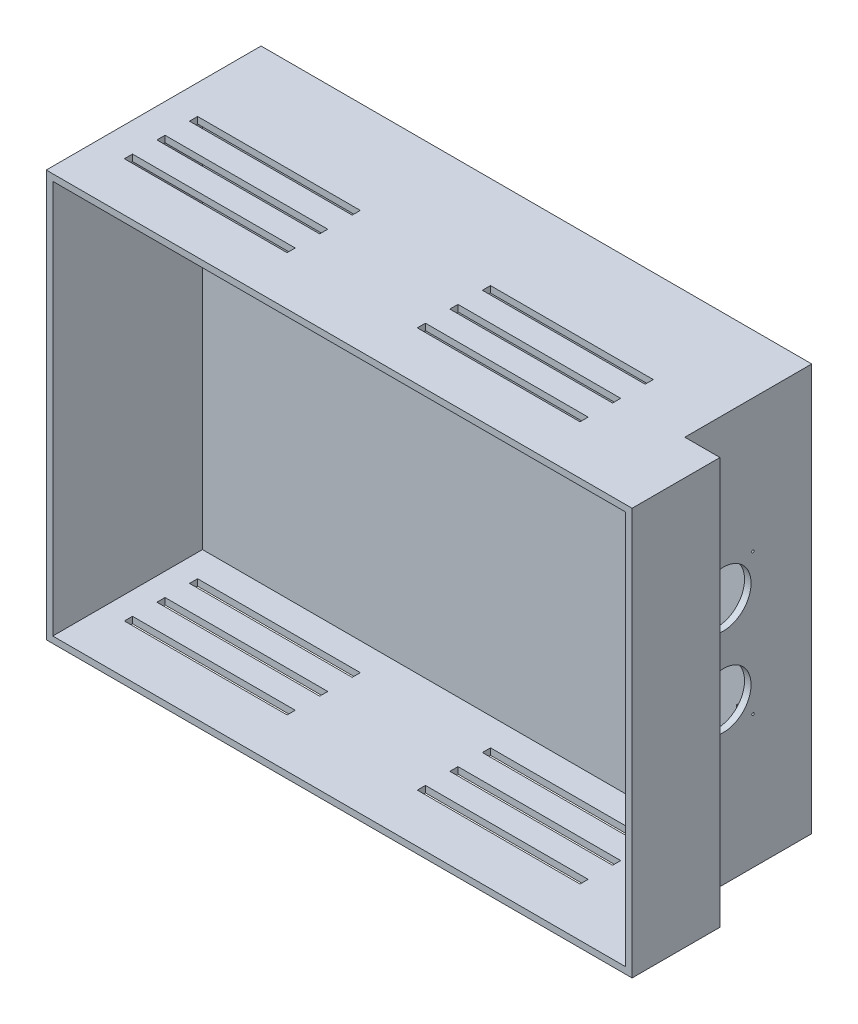
SolidWorks part; units mm, degrees
ref_plane "前视基准面" through (0, 0, 0) normal (0, 0, 1) x (1, 0, 0)
ref_plane "上视基准面" through (0, 0, 0) normal (0, 1, 0) x (1, 0, 0)
ref_plane "右视基准面" through (0, 0, 0) normal (1, 0, 0) x (0, 0, -1)
sketch "草图2" plane through (0, 0, 0) normal (0, 0, 1) x (1, 0, 0)
  line L1 (-90, 62.5) -> (90, 62.5)
  line L2 (-90, 62.5) -> (-90, -62.5)
  line L3 (-90, -62.5) -> (90, -62.5)
  line L4 (90, 62.5) -> (90, -62.5)
  line L5 (-90, 62.5) -> (90, -62.5) construction
  line L6 (-90, -62.5) -> (90, 62.5) construction
  point P0 (0, 0)
  dimension "D1" = 180
  dimension "D2" = 125
extrude "凸台-拉伸1" add sketch "草图2" along normal blind 66
sketch "草图3" plane through (0, 0, 0) normal (0, 0, -1) x (-1, 0, 0)
  line L1 (87, -59.5) -> (-50, -59.5)
  line L2 (87, -59.5) -> (87, 59.5)
  line L3 (87, 59.5) -> (-50, 59.5)
  line L4 (-50, -59.5) -> (-50, 59.5)
  line L5 (-90, 62.5) -> (90, 62.5) construction
  line L6 (90, 62.5) -> (90, -62.5) construction
  line L7 (90, -62.5) -> (-90, -62.5) construction
  line L9 (-90, -62.5) -> (-90, 62.5) construction
  dimension "D1" = 3
  dimension "D2" = 3
  dimension "D3" = 3
  dimension "D4" = 40
extrude "切除-拉伸1" cut sketch "草图3" against normal blind 18
sketch "草图4" plane through (90, 0, 0) normal (1, 0, 0) x (0, 0, -1)
  line L0 (-39, -62.5) -> (-39, 62.5)
  line L1 (-66, 62.5) -> (-66, -62.5) construction
  line L2 (-66, 62.5) -> (0, 62.5) construction
  line L4 (0, -62.5) -> (0, 62.5)
  line L6 (-66, 62.5) -> (-66, -62.5)
  line L9 (0, 62.5) -> (-39, 62.5)
  line L11 (-39, -62.5) -> (0, -62.5)
  line L14 (0, -62.5) -> (0, 62.5)
  line L15 (0, 62.5) -> (-66, 62.5)
  line L16 (-66, -62.5) -> (0, -62.5)
  dimension "D2" = 27
  dimension "D1" = 0
extrude "切除-拉伸2" cut sketch "草图4" against normal offset from surface (10.8 mm away) 2
shell "抽壳1" thickness 2 removed face at (0, 0, 66)
sketch "草图6" plane through (79.2, 0, 0) normal (1, 0, 0) x (0, 0, -1)
  line L1 (-16.0647, -23.6651) -> (-20.0647, -23.6651)
  line L2 (-16.0647, -23.6651) -> (-16.0647, -19.6651)
  line L3 (-16.0647, -19.6651) -> (-20.0647, -19.6651)
  line L4 (-20.0647, -23.6651) -> (-20.0647, -19.6651)
  line L5 (-34.2212, -23.6651) -> (-38.2212, -23.6651)
  line L6 (-34.2212, -23.6651) -> (-34.2212, -19.6651)
  line L7 (-34.2212, -19.6651) -> (-38.2212, -19.6651)
  line L8 (-38.2212, -23.6651) -> (-38.2212, -19.6651)
  line L9 (-34.2212, 19.6651) -> (-38.2212, 19.6651)
  line L10 (-34.2212, 19.6651) -> (-34.2212, 23.6651)
  line L11 (-34.2212, 23.6651) -> (-38.2212, 23.6651)
  line L12 (-38.2212, 19.6651) -> (-38.2212, 23.6651)
  line L13 (-16.0647, 19.6651) -> (-20.0647, 19.6651)
  line L14 (-16.0647, 19.6651) -> (-16.0647, 23.6651)
  line L15 (-16.0647, 23.6651) -> (-20.0647, 23.6651)
  line L16 (-20.0647, 19.6651) -> (-20.0647, 23.6651)
  arc A0 (-18.5647, 21.6651) -> (-17.5647, 21.6651) centre (-18.0647, 21.6651) ccw construction
  arc A1 (-17.5647, 21.6651) -> (-18.5647, 21.6651) centre (-18.0647, 21.6651) ccw construction
  arc A2 (-35.7212, 21.6651) -> (-36.7212, 21.6651) centre (-36.2212, 21.6651) ccw construction
  arc A3 (-36.7212, 21.6651) -> (-35.7212, 21.6651) centre (-36.2212, 21.6651) ccw construction
  arc A4 (-36.7212, -21.6651) -> (-35.7212, -21.6651) centre (-36.2212, -21.6651) ccw construction
  arc A5 (-18.5647, -21.6651) -> (-17.5647, -21.6651) centre (-18.0647, -21.6651) ccw construction
  circle A6 centre (-27.143, 43.5) radius 8.15
  circle A7 centre (-27.143, -43.5) radius 8.15
  circle A8 centre (-27.143, -43.5) radius 7.65 construction
  dimension "D10" = 2
  dimension "D17" = 0.5
  dimension "D1" = 2
  dimension "D2" = 2
  dimension "D3" = 2
  dimension "D4" = 2
  dimension "D5" = 4
  dimension "D6" = 2
  dimension "D7" = 4
  dimension "D8" = 2
  dimension "D9" = 2
  dimension "D11" = 4
  dimension "D12" = 4
  dimension "D13" = 2
  dimension "D14" = 2
  dimension "D15" = 4
  dimension "D16" = 4
extrude "凸台-拉伸2" add sketch "草图6" against normal up to surface (3 mm away)
sketch "草图7" plane through (79.2, 0, 0) normal (1, 0, 0) x (0, 0, -1)
  circle A0 centre (-27.143, -13.5) radius 8.5
  circle A1 centre (-27.143, 13.5) radius 8.5
  circle A2 centre (-18.0647, -21.6651) radius 0.375
  circle A3 centre (-18.0647, 21.6651) radius 0.375
  circle A4 centre (-36.2212, 21.6651) radius 0.375
  circle A5 centre (-36.2212, -21.6651) radius 0.375
  arc A6 (-19.143, -13.5) -> (-35.143, -13.5) centre (-27.143, -13.5) ccw construction
  dimension "D1" = 0.75
  dimension "D2" = 0.5
extrude "切除-拉伸3" cut sketch "草图7" against normal up to next
sketch "草图8" plane through (0, -62.5, 0) normal (0, -1, 0) x (1, 0, 0)
  line L0 (-90, 66) -> (90, 66) construction
  line L1 (-81, 51) -> (-31, 51)
  line L2 (-81, 51) -> (-81, 48.5)
  line L3 (-81, 48.5) -> (-31, 48.5)
  line L4 (-31, 51) -> (-31, 48.5)
  line L5 (-90, 66) -> (-90, 0) construction
  line L6 (9, 51) -> (59, 51)
  line L7 (9, 51) -> (9, 48.5)
  line L8 (9, 48.5) -> (59, 48.5)
  line L9 (59, 51) -> (59, 48.5)
  line L10 (9, 41) -> (59, 41)
  line L11 (9, 41) -> (9, 38.5)
  line L12 (9, 38.5) -> (59, 38.5)
  line L13 (59, 41) -> (59, 38.5)
  line L14 (9, 31) -> (59, 31)
  line L15 (9, 31) -> (9, 28.5)
  line L16 (9, 28.5) -> (59, 28.5)
  line L17 (59, 31) -> (59, 28.5)
  line L18 (-81, 41) -> (-31, 41)
  line L19 (-81, 41) -> (-81, 38.5)
  line L20 (-81, 38.5) -> (-31, 38.5)
  line L21 (-31, 41) -> (-31, 38.5)
  line L22 (-81, 31) -> (-31, 31)
  line L23 (-81, 31) -> (-81, 28.5)
  line L24 (-81, 28.5) -> (-31, 28.5)
  line L25 (-31, 31) -> (-31, 28.5)
  dimension "D1" = 2.5
  dimension "D2" = 15
  dimension "D3" = 9
  dimension "D4" = 50
  dimension "D5" = 2
  dimension "D6" = 3
extrude "切除-拉伸4" cut sketch "草图8" against normal up to surface (125 mm away) and the other way through all up to face at (26.4, 62.5, 35)
